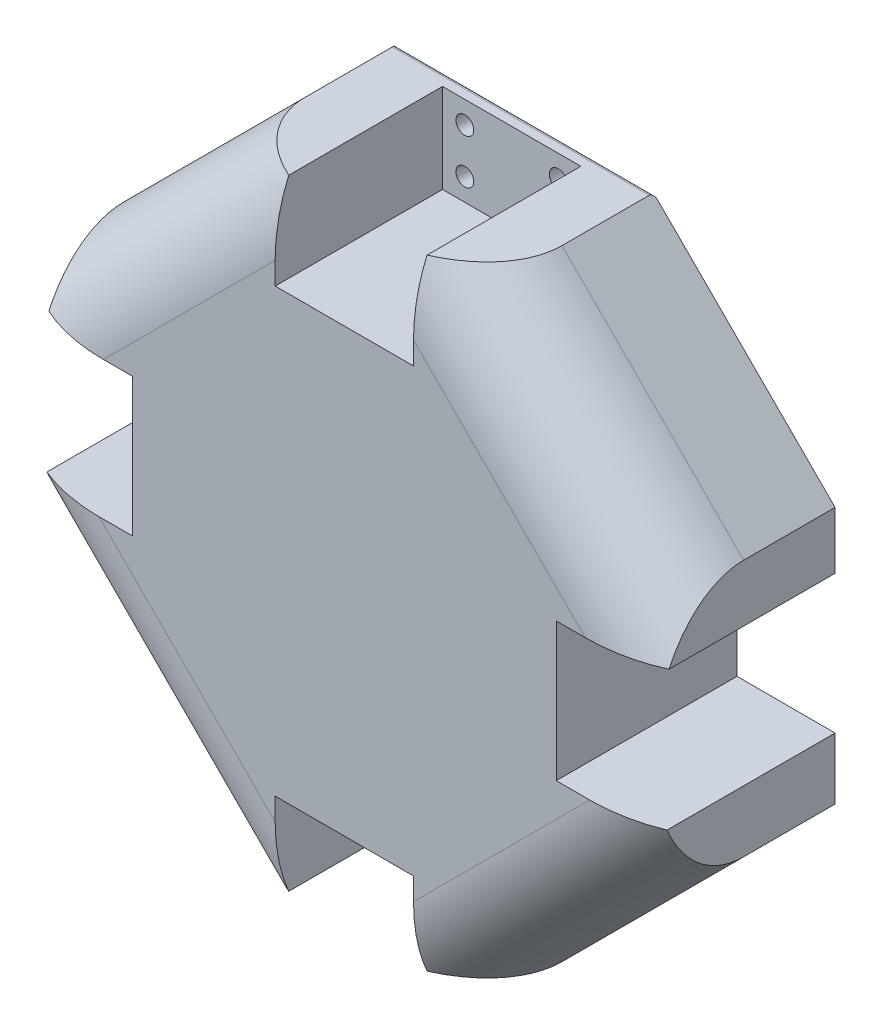
SolidWorks part; units mm, degrees
ref_plane "Plano frontal" through (0, 0, 0) normal (0, 0, 1) x (1, 0, 0)
ref_plane "Plano superior" through (0, 0, 0) normal (0, 1, 0) x (1, 0, 0)
ref_plane "Plano direito" through (0, 0, 0) normal (1, 0, 0) x (0, 0, -1)
sketch "Esboço1" plane through (0, 0, 0) normal (0, 0, 1) x (1, 0, 0)
  line L0 (-16.0007, -69) -> (-16.0007, -49)
  line L1 (69, -28.5807) -> (69, -15.5007)
  line L2 (69, 28.5807) -> (28.5807, 69)
  line L3 (28.5807, 69) -> (15.9993, 69)
  line L4 (-28.5807, 69) -> (-69, 28.5807)
  line L5 (-69, 28.5807) -> (-69, 16.4993)
  line L6 (-69, -28.5807) -> (-28.5807, -69)
  line L7 (-28.5807, -69) -> (-16.0007, -69)
  line L8 (28.5807, -69) -> (69, -28.5807)
  line L9 (-16.0007, -49) -> (15.9993, -49)
  line L10 (15.9993, -49) -> (15.9993, -69)
  line L11 (15.9993, -69) -> (28.5807, -69)
  line L12 (0, 0) -> (70, 0) construction
  line L13 (15.9993, 49) -> (15.9993, 69)
  line L14 (-16.0007, 49) -> (15.9993, 49)
  line L15 (-16.0007, 69) -> (-16.0007, 49)
  line L16 (-16.0007, 69) -> (-28.5807, 69)
  line L17 (-69, -15.5007) -> (-47, -15.5007)
  line L18 (-47, -15.5007) -> (-47, 16.4993)
  line L19 (-47, 16.4993) -> (-69, 16.4993)
  line L20 (-69, -15.5007) -> (-69, -28.5807)
  line L21 (0, -48.3451) -> (0, 0) construction
  line L22 (0, 0) -> (0, 117.9622) construction
  line L23 (69, -15.5007) -> (47, -15.5007)
  line L24 (47, -15.5007) -> (47, 16.4993)
  line L25 (47, 16.4993) -> (69, 16.4993)
  line L26 (69, 16.4993) -> (69, 28.5807)
  circle A0 centre (0, 0) radius 69 construction
  dimension "D1" = 138
  dimension "D2" = 20
  dimension "D3" = 12.58
  dimension "D4" = 32
  dimension "D5" = 32
  dimension "D6" = 22
  dimension "D7" = 13.08
extrude "Ressalto-extrusão1" add sketch "Esboço1" along normal blind 40 contours L4 L5 L19 L18 L17 L20 L6 L7 L0 L9 L10 L11 L8 L1 L23 L24 L25 L26 L2 L3 L13 L14 L15 L16
shell "Casca1" thickness 0.5 removed face at (-0.0002, 0.1664, 0) outward yes
sketch "Esboço2" plane through (0, 0, 0) normal (0, 0, 1) x (1, 0, 0)
  line L1 (15.4993, -49.5) -> (-15.5007, -49.5)
  line L2 (15.4993, -49.5) -> (15.4993, -69.5)
  line L3 (15.4993, -69.5) -> (-15.5007, -69.5)
  line L4 (-15.5007, -49.5) -> (-15.5007, -69.5)
  line L5 (15.4993, 49.5) -> (-15.5007, 49.5)
  line L6 (15.4993, 49.5) -> (15.4993, 69.5)
  line L7 (15.4993, 69.5) -> (-15.5007, 69.5)
  line L8 (-15.5007, 49.5) -> (-15.5007, 69.5)
extrude "Ressalto-extrusão2" add sketch "Esboço2" along normal blind 3 contours L7 L8 L5 L6 | L3 L4 L1 L2
fillet "Filete1" radius 20 4 edges at (-49.1439, 49.1439, 40.5) (49.1439, -49.1439, 40.5) (-49.1439, -49.1439, 40.5) (49.1439, 49.1439, 40.5)
fillet "Filete2" radius 20 4 edges at (-48.7904, 48.7904, 40) (-48.7904, -48.7904, 40) (48.7904, -48.7904, 40) (48.7904, 48.7904, 40)
sketch "Esboço3" plane through (0, 0, 3) normal (0, 0, 1) x (1, 0, 0)
  line L0 (15.4993, -69.5) -> (-15.5007, -69.5) construction
  line L1 (-15.5007, -49.5) -> (-15.5007, -69.5) construction
  line L2 (15.4993, -49.5) -> (-15.5007, -49.5) construction
  line L3 (15.4993, -49.5) -> (15.4993, -69.5) construction
  line L4 (0, 0) -> (75.5473, 0) construction
  circle A0 centre (-10.5007, -54.5) radius 2
  circle A1 centre (-10.5007, -64.5) radius 2
  circle A2 centre (10.4393, -64.5) radius 2
  circle A3 centre (10.4393, -54.5) radius 2
  circle A4 centre (10.4393, 54.5) radius 2
  circle A5 centre (10.4393, 64.5) radius 2
  circle A6 centre (-10.5007, 64.5) radius 2
  circle A7 centre (-10.5007, 54.5) radius 2
  dimension "D1" = 4
  dimension "D4" = 4
  dimension "D6" = 5
  dimension "D7" = 4
  dimension "D9" = 5.06
  dimension "D10" = 4
  dimension "D11" = 5.06
  dimension "D12" = 5
  dimension "D2" = 5
  dimension "D3" = 5
  dimension "D5" = 5
  dimension "D8" = 5
extrude "Corte-extrusão1" cut sketch "Esboço3" against normal through all
fillet "Filete3" radius 1 1 edges at (0, -69.5, 0)
fillet "Filete4" radius 1 1 edges at (0, 69.5, 0)
